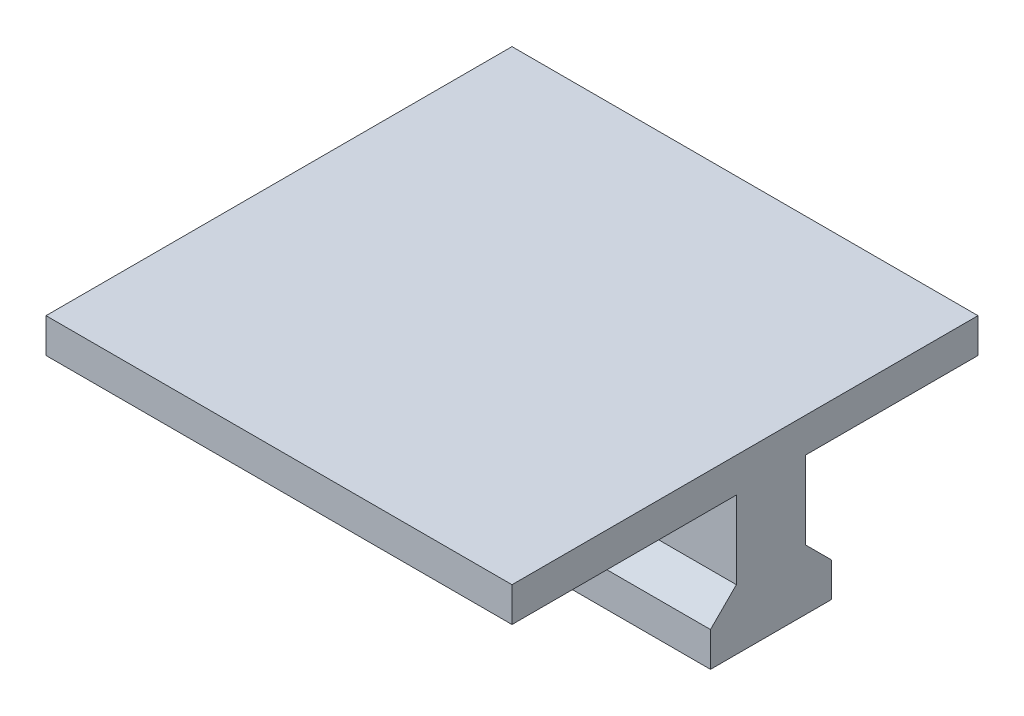
SolidWorks part; units mm, degrees
ref_plane "Front Plane" through (0, 0, 0) normal (0, 0, 1) x (1, 0, 0)
ref_plane "Top Plane" through (0, 0, 0) normal (0, 1, 0) x (1, 0, 0)
ref_plane "Right Plane" through (0, 0, 0) normal (1, 0, 0) x (0, 0, -1)
sketch "Sketch1" plane through (0, 0, 0) normal (0, 1, 0) x (1, 0, 0)
  line L1 (-13.5, -13.5) -> (13.5, -13.5)
  line L2 (-13.5, -13.5) -> (-13.5, 13.5)
  line L3 (-13.5, 13.5) -> (13.5, 13.5)
  line L4 (13.5, -13.5) -> (13.5, 13.5)
  line L5 (-13.5, -13.5) -> (13.5, 13.5) construction
  line L6 (-13.5, 13.5) -> (13.5, -13.5) construction
  point P0 (0, 0)
  dimension "D1" = 27
  dimension "D2" = 27
extrude "Boss-Extrude1" add sketch "Sketch1" along normal blind 2
sketch "Sketch2" plane through (0, 0, 0) normal (0, -1, 0) x (1, 0, 0)
  line L0 (13.5, 13.5) -> (13.5, -13.5) construction
  line L1 (-13.5, -3.5) -> (13.5, -3.5)
  line L2 (-13.5, -3.5) -> (-13.5, 0.5)
  line L3 (-13.5, 0.5) -> (13.5, 0.5)
  line L4 (13.5, -3.5) -> (13.5, 0.5)
  line L5 (-13.5, -3.5) -> (13.5, 0.5) construction
  line L6 (-13.5, 0.5) -> (13.5, -3.5) construction
  line L7 (13.5, -13.5) -> (-13.5, -13.5) construction
  point P0 (0, -1.5)
  dimension "D1" = 4
  dimension "D2" = 10
extrude "Boss-Extrude2" add sketch "Sketch2" along normal blind 8
sketch "Sketch3" plane through (0, -8, 0) normal (0, -1, 0) x (1, 0, 0)
  line L0 (13.5, 13.5) -> (13.5, 0.5) construction
  line L1 (-13.5, -5) -> (13.5, -5)
  line L2 (-13.5, -5) -> (-13.5, 2)
  line L3 (-13.5, 2) -> (13.5, 2)
  line L4 (13.5, -5) -> (13.5, 2)
  line L5 (-13.5, -5) -> (13.5, 2) construction
  line L6 (-13.5, 2) -> (13.5, -5) construction
  line L7 (13.5, 0.5) -> (-13.5, 0.5) construction
  point P0 (0, -1.5)
  dimension "D1" = 7
  dimension "D2" = 1.5
extrude "Boss-Extrude3" add sketch "Sketch3" against normal blind 2
chamfer "Chamfer1" distance 1.5 angle 45 2 edges at (0, -6, -3.5) (0, -6, 0.5)
